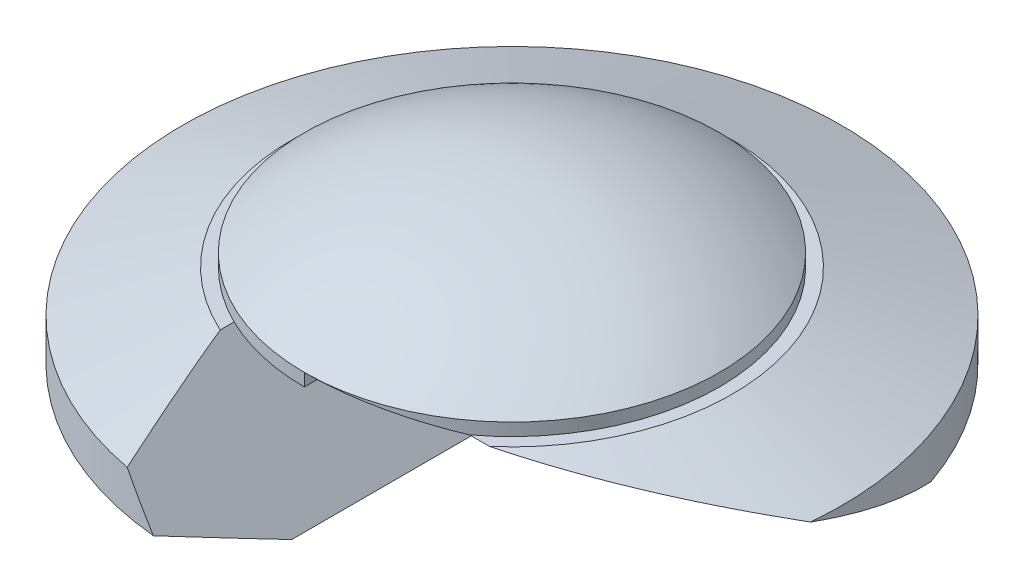
SolidWorks part; units mm, degrees
ref_plane "Alzado" through (0, 0, 0) normal (0, 0, 1) x (1, 0, 0)
ref_plane "Planta" through (0, 0, 0) normal (0, 1, 0) x (1, 0, 0)
ref_plane "Vista lateral" through (0, 0, 0) normal (1, 0, 0) x (0, 0, -1)
sketch "Croquis1" plane through (0, 0, 0) normal (0, 1, 0) x (1, 0, 0)
  circle A0 centre (0, 0) radius 52.5
  dimension "D1" = 105
extrude "Saliente-Extruir1" add sketch "Croquis1" along normal blind 10 draft 69 draft outward yes
sketch "Croquis2" plane through (0, 10, 0) normal (0, 1, 0) x (1, 0, 0)
  circle A0 centre (0, 0) radius 78.5509
  dimension "D1" = 157.1018
extrude "Saliente-Extruir2" add sketch "Croquis2" along normal blind 10
sketch "Croquis3" plane through (0, 20, 0) normal (0, 1, 0) x (1, 0, 0)
  circle A0 centre (0, 0) radius 78.5509
extrude "Saliente-Extruir3" add sketch "Croquis3" along normal blind 10 draft 69
sketch "Croquis4" plane through (0, 30, 0) normal (0, 1, 0) x (1, 0, 0)
  circle A0 centre (0, 0) radius 49.5
  dimension "D1" = 99
extrude "Saliente-Extruir4" add sketch "Croquis4" along normal blind 3
dome "Cúpula1" faces to dome 1 distance 16 reverse direction no elliptical dome no face at (0, 33, 49.5) parameters "D1"=16
sketch "Croquis6" plane through (0, 0, 0) normal (1, 0, 0) x (0, 0, -1)
  line L0 (-49.5, 33) -> (55.0644, 0.9844)
  line L1 (52.5, 0) -> (78.5509, 10) construction
  line L2 (-49.5, 33) -> (-78.5509, 20)
  line L3 (-78.5509, 20) -> (-78.5509, 10)
  line L4 (-78.5509, 10) -> (-52.5, 0)
  line L5 (-52.5, 0) -> (52.5, 0)
  line L6 (52.5, 0) -> (55.0644, 0.9844)
  dimension "D1" = 109.3559
extrude "Cortar-Extruir1" cut sketch "Croquis6" along normal through all
ref_plane "Plano1" through (0, 0, 78.5509) normal (0, 0, 1) x (1, 0, 0)
sketch "Croquis9" plane through (0, 0, 78.5509) normal (0, 0, 1) x (1, 0, 0)
  line L0 (0, 0) -> (-21.7963, 30)
  line L1 (52.5, 30) -> (-52.5, 30) construction
  line L2 (-21.7963, 30) -> (0, 30)
  line L3 (0, 30) -> (0, 0)
  line L4 (0, 0) -> (-17.4434, 0)
  line L5 (-52.5, 0) -> (0, 0) construction
  dimension "D1" = 54
extrude "Cortar-Extruir3" cut sketch "Croquis9" against normal up to surface (136.8303 mm away) contours L3 L0 L2 up to face at (36.8046, 20.5658, 8.8894)
ref_plane "Plano2" through (-49.5, 0, 0) normal (-1, 0, 0) x (0, 0, 1)
